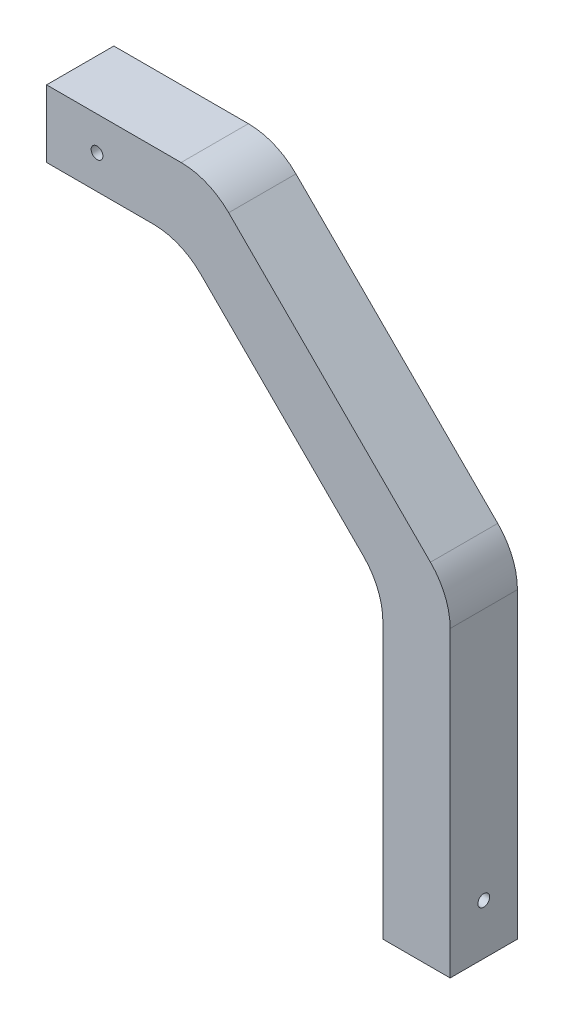
SolidWorks part; units mm, degrees
ref_plane "Alzado" through (0, 0, 0) normal (0, 0, 1) x (1, 0, 0)
ref_plane "Planta" through (0, 0, 0) normal (0, 1, 0) x (1, 0, 0)
ref_plane "Vista lateral" through (0, 0, 0) normal (1, 0, 0) x (0, 0, -1)
sketch "Croquis1" plane through (0, 0, 0) normal (0, 0, 1) x (1, 0, 0)
  line L0 (-60, 0) -> (60, 0) construction
  line L1 (-60, 0) -> (-11.7157, 0)
  line L2 (-11.7157, 0) -> (60, -71.7157)
  line L3 (60, -71.7157) -> (60, -170)
  line L4 (60, -170) -> (40, -170)
  line L5 (40, -170) -> (40, -80)
  line L6 (40, -80) -> (-20, -20)
  line L7 (-20, -20) -> (-60, -20)
  line L8 (-60, -20) -> (-60, 0)
  line L9 (60, -170) -> (60, -160) construction
  line L10 (-60, -10) -> (-45, -10) construction
  line L11 (50, -170) -> (50, -155) construction
  circle A0 centre (-45, -10) radius 1.75
  point P0 (-60, -10)
  point P4 (0, 0)
  dimension "D9" = 3.5
  dimension "D1" = 150
  dimension "D2" = 120
  dimension "D3" = 20
  dimension "D4" = 20
  dimension "D5" = 20
  dimension "D6" = 90
  dimension "D7" = 40
  dimension "D8" = 10
  dimension "D10" = 15
  dimension "D11" = 15
extrude "Saliente-Extruir1" add sketch "Croquis1" along normal blind 20 contours L1 L2 L3 L4 L5 L6 L7 L8 | A0
sketch "Croquis2" plane through (0, 0, 20) normal (0, 0, 1) x (1, 0, 0)
  line L0 (-60, -20) -> (-20, -20)
  line L1 (-20, -20) -> (-20, 0)
  line L2 (-60, 0) -> (-11.7157, 0) construction
  line L3 (-20, 0) -> (-60, 0)
  line L4 (-60, 0) -> (-60, -20)
extrude "Cortar-Extruir1" [suppressed] cut sketch "Croquis2" against normal blind 10
sketch "Croquis3" plane through (60, 0, 0) normal (1, 0, 0) x (0, 0, -1)
  line L0 (-20, -170) -> (0, -170)
  line L1 (0, -170) -> (0, -150)
  line L2 (0, -71.7157) -> (0, -170) construction
  line L3 (0, -150) -> (-20, -150)
  line L4 (-20, -71.7157) -> (-20, -170) construction
  line L5 (-20, -150) -> (-20, -170)
  dimension "D1" = 20
extrude "Cortar-Extruir2" [suppressed] cut sketch "Croquis3" against normal blind 10
fillet "Redondeo1" radius 20 4 edges at (40, -80, 10) (60, -71.7157, 10) (-20, -20, 10) (-11.7157, 0, 10)
sketch "Croquis4" plane through (40, 0, 0) normal (-1, 0, 0) x (0, 0, 1)
  line L0 (10, -170) -> (10, -155) construction
  line L1 (20, -170) -> (0, -170) construction
  circle A0 centre (10, -155) radius 1.75
  dimension "D2" = 3.5
  dimension "D1" = 15
extrude "Cortar-Extruir3" cut sketch "Croquis4" against normal blind 20
